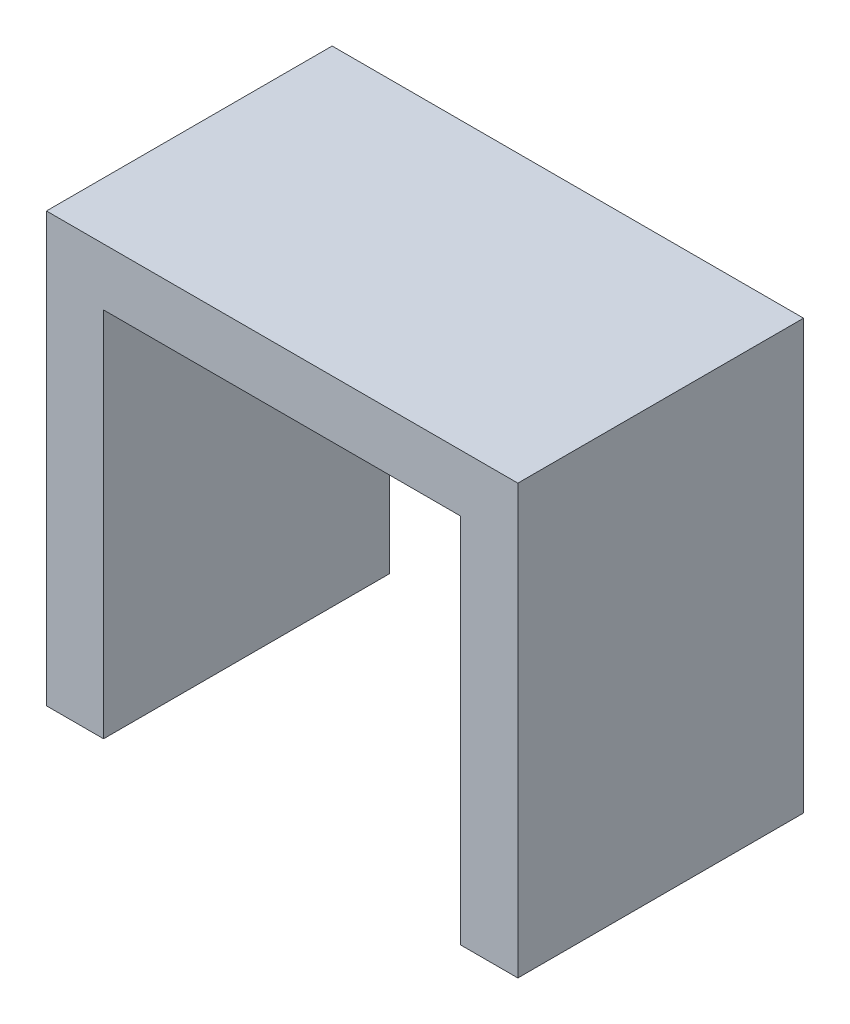
SolidWorks part; units mm, degrees
ref_plane "Front Plane" through (0, 0, 0) normal (0, 0, 1) x (1, 0, 0)
ref_plane "Top Plane" through (0, 0, 0) normal (0, 1, 0) x (1, 0, 0)
ref_plane "Right Plane" through (0, 0, 0) normal (1, 0, 0) x (0, 0, -1)
sketch "Sketch1" plane through (0, 0, 0) normal (0, 0, 1) x (1, 0, 0)
  line L0 (-12.5988, 0) -> (-10.5988, 0)
  line L1 (-10.5988, 0) -> (-10.5988, 13)
  line L2 (-10.5988, 13) -> (1.9012, 13)
  line L3 (1.9012, 13) -> (1.9012, 0)
  line L4 (1.9012, 0) -> (3.9012, 0)
  line L5 (3.9012, 0) -> (3.9012, 15)
  line L6 (3.9012, 15) -> (-12.5988, 15)
  line L7 (-12.5988, 15) -> (-12.5988, 0)
  dimension "D1" = 12.5
  dimension "D3" = 2
  dimension "D4" = 2
  dimension "D6" = 13
  dimension "D7" = 2
extrude "Boss-Extrude1" add sketch "Sketch1" along normal blind 10
